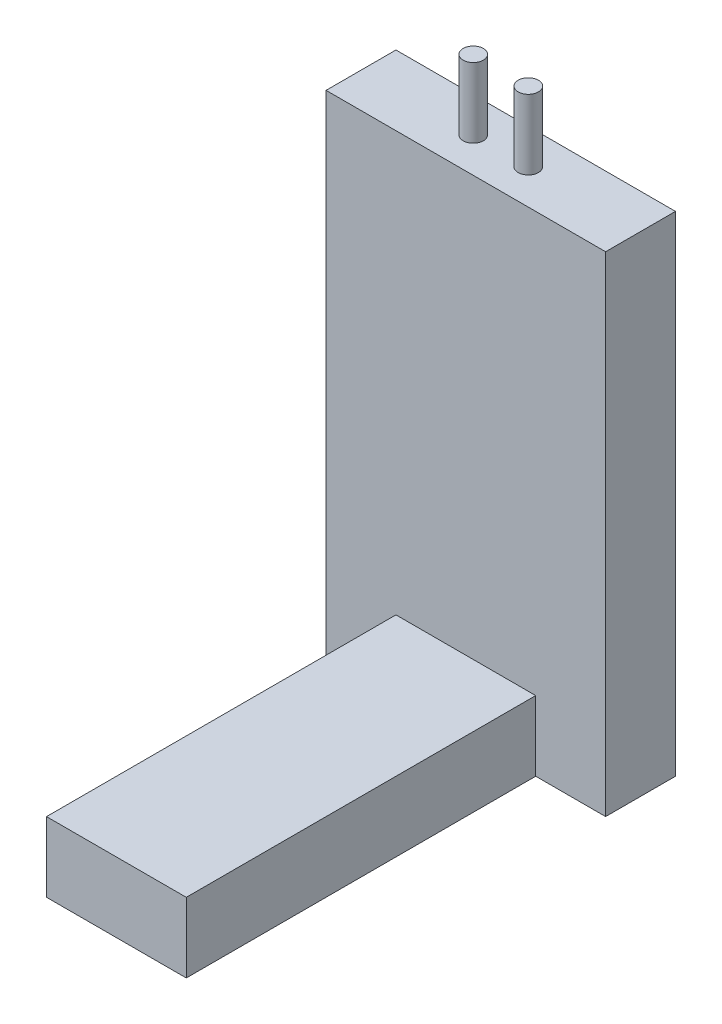
SolidWorks part; units mm, degrees
ref_plane "Front Plane" through (0, 0, 0) normal (0, 0, 1) x (1, 0, 0)
ref_plane "Top Plane" through (0, 0, 0) normal (0, 1, 0) x (1, 0, 0)
ref_plane "Right Plane" through (0, 0, 0) normal (1, 0, 0) x (0, 0, -1)
sketch "Sketch3" plane through (0, 0, 0) normal (0, 1, 0) x (1, 0, 0)
  line L0 (-25.4, 0) -> (76.2, 0)
  line L1 (-25.4, 0) -> (-25.4, 25.4)
  line L2 (-25.4, 25.4) -> (76.2, 25.4)
  line L3 (76.2, 25.4) -> (76.2, 0)
extrude "Boss-Extrude1" add sketch "Sketch3" along normal blind 177.8
sketch "Sketch6" plane through (0, 177.8, 0) normal (0, 1, 0) x (1, 0, 0)
  line L0 (25.4, 25.4) -> (25.4, 0) construction
  line L1 (76.2, 25.4) -> (-25.4, 25.4) construction
  line L2 (-25.4, 0) -> (76.2, 0) construction
  line L3 (25.4, 12.7) -> (15.4, 12.7) construction
  line L5 (25.4, 12.7) -> (35.4, 12.7) construction
  circle A0 centre (15.4, 12.7) radius 3.683
  circle A2 centre (35.4, 12.7) radius 3.683
  dimension "D1" = 7.366
  dimension "D2" = 7.366
extrude "Boss-Extrude4" add sketch "Sketch6" along normal blind 25.4
sketch "Sketch7" plane through (0, 0, 0) normal (0, -1, 0) x (-1, 0, 0)
  line L0 (-25.4, 12.7) -> (5.08, 12.7) construction
  line L2 (-25.4, 25.4) -> (-25.4, 12.7) construction
  line L3 (-25.4, 12.7) -> (-55.88, 12.7) construction
  line L4 (-76.2, 25.4) -> (25.4, 25.4) construction
  circle A1 centre (5.08, 12.7) radius 5.207
  circle A2 centre (-55.88, 12.7) radius 5.207
  dimension "D1" = 10.414
  dimension "D2" = 10.414
extrude "Cut-Extrude1" cut sketch "Sketch7" against normal blind 17.78
sketch "Sketch8" plane through (0, 0, 0) normal (0, 0, 1) x (1, 0, 0)
  line L0 (25.4, 0) -> (25.4, 25.4) construction
  line L1 (-25.4, 0) -> (76.2, 0) construction
  line L2 (25.4, 25.4) -> (50.8, 25.4) construction
  line L3 (25.4, 25.4) -> (0, 25.4) construction
  line L5 (0, 25.4) -> (50.8, 25.4)
  line L6 (0, 25.4) -> (0, 0)
  line L7 (0, 0) -> (50.8, 0)
  line L8 (50.8, 25.4) -> (50.8, 0)
extrude "Boss-Extrude5" add sketch "Sketch8" along normal blind 127
